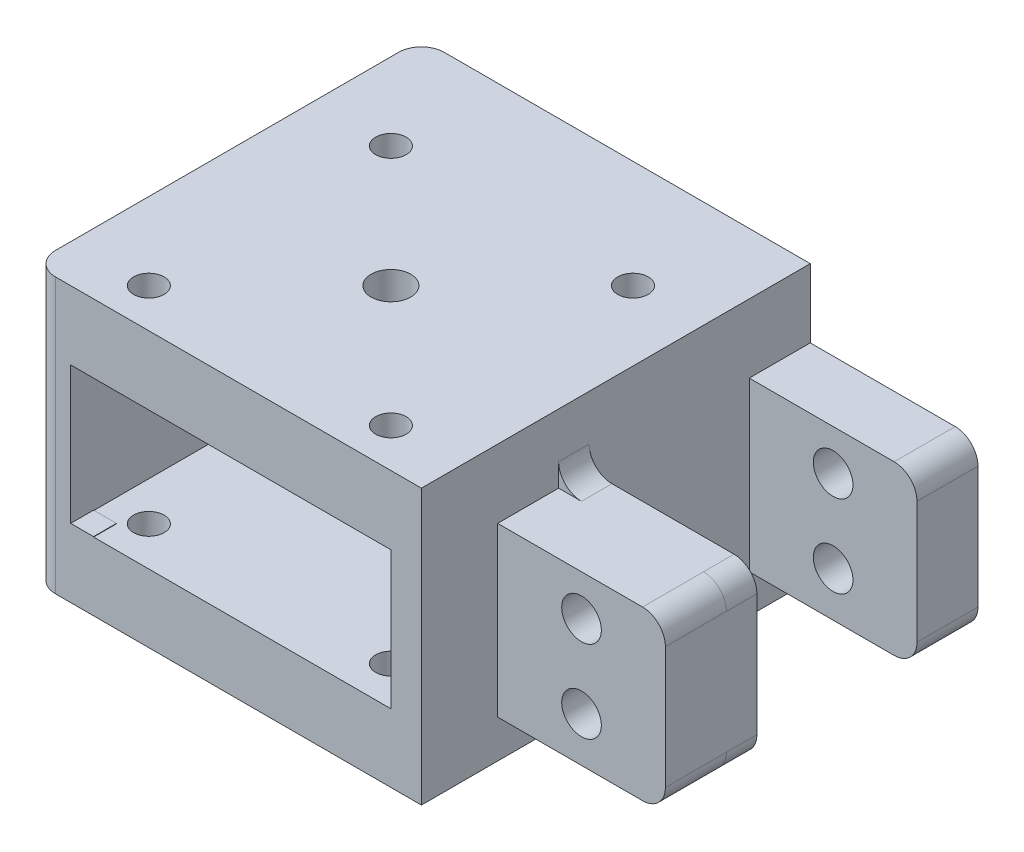
SolidWorks part; units mm, degrees
ref_plane "Front Plane" through (0, 0, 0) normal (0, 0, 1) x (1, 0, 0)
ref_plane "Top Plane" through (0, 0, 0) normal (0, 1, 0) x (1, 0, 0)
ref_plane "Right Plane" through (0, 0, 0) normal (1, 0, 0) x (0, 0, -1)
sketch "Sketch1" plane through (0, 0, 0) normal (0, 0, 1) x (1, 0, 0)
  line L1 (-11, -11) -> (11, -11)
  line L2 (-11, -11) -> (-11, 11)
  line L3 (-11, 11) -> (11, 11)
  line L4 (11, -11) -> (11, 11)
  line L5 (-11, -11) -> (11, 11) construction
  line L6 (-11, 11) -> (11, -11) construction
  point P0 (0, 0)
  dimension "D1" = 22
  dimension "D2" = 22
extrude "Boss-Extrude2" add sketch "Sketch1" along normal blind 4
sketch "Sketch3" plane through (0, 0, 4) normal (0, 0, 1) x (1, 0, 0)
  line L1 (-11, 11) -> (-15, 11)
  line L2 (-11, 11) -> (-11, -11)
  line L3 (-11, -11) -> (-15, -11)
  line L4 (-15, 11) -> (-15, -11)
  dimension "D1" = 4
extrude "Boss-Extrude3" add sketch "Sketch3" against normal blind 24
sketch "Sketch4" plane through (0, 11, 0) normal (0, 1, 0) x (1, 0, 0)
  line L1 (-11, 20) -> (-15, 20)
  line L2 (-11, 20) -> (-11, -4)
  line L3 (-11, -4) -> (-15, -4)
  line L4 (-15, 20) -> (-15, -4)
extrude "Boss-Extrude4" add sketch "Sketch4" along normal blind 4
sketch "Sketch5" plane through (-11, 0, 0) normal (1, 0, 0) x (0, 0, -1)
  line L1 (-4, 11) -> (20, 11)
  line L2 (-4, 11) -> (-4, 15)
  line L3 (-4, 15) -> (20, 15)
  line L4 (20, 11) -> (20, 15)
extrude "Boss-Extrude5" add sketch "Sketch5" against normal blind 24
sketch "Sketch6" plane through (-15, 0, 0) normal (-1, 0, 0) x (0, 0, 1)
  line L1 (-20, -11) -> (22, -11)
  line L2 (-20, -11) -> (-20, -7.0561)
  line L3 (-20, -7.0561) -> (22, -7.0561)
  line L4 (22, -11) -> (22, -7.0561)
  dimension "D1" = 42
extrude "Boss-Extrude6" add sketch "Sketch6" along normal blind 42
sketch "Sketch8" plane through (0, 15, 0) normal (0, 1, 0) x (1, 0, 0)
  line L0 (-11, 20) -> (-35, 20) construction
  line L1 (-57, -22) -> (-15, -22)
  line L2 (-57, -22) -> (-57, 20)
  line L3 (-57, 20) -> (-15, 20)
  line L4 (-15, -22) -> (-15, 20)
  line L5 (-57, 20) -> (-15, 20) construction
extrude "Boss-Extrude7" add sketch "Sketch8" against normal blind 4
sketch "Sketch9" plane through (0, -11, 0) normal (0, -1, 0) x (1, 0, 0)
  circle A0 centre (-36, 1) radius 11.5
  dimension "D1" = 23
extrude "Cut-Extrude1" cut sketch "Sketch9" against normal blind 4
sketch "Sketch10" plane through (0, 15, 0) normal (0, 1, 0) x (1, 0, 0)
  circle A0 centre (-34, -1) radius 2.6
  dimension "D1" = 5.2
extrude "Cut-Extrude2" cut sketch "Sketch10" against normal blind 4
sketch "Sketch11" plane through (0, 0, 4) normal (0, 0, 1) x (1, 0, 0)
  circle A0 centre (0, 5.6604) radius 2.6
  circle A1 centre (0, -5.136) radius 2.6
  dimension "D1" = 5.2
  dimension "D2" = 5.2
extrude "Cut-Extrude3" cut sketch "Sketch11" against normal blind 4
fillet "Fillet1" radius 3 10 edges at (-11, 11, 2) (11, 11, 2) (11, -11, 2) (-15, -9.0281, 22) (-57, -9.0281, 22) (-57, -9.0281, -20) (-57, 13, -20) (-11, 2, -20) (-15, 13, 22) (-57, 13, 22)
sketch "Sketch12" plane through (0, 15, 0) normal (0, 1, 0) x (1, 0, 0)
  line L1 (-40.0637, -6.0537) -> (-28.4493, -6.0537)
  line L2 (-40.0637, -6.0537) -> (-40.0637, 3.8424)
  line L3 (-40.0637, 3.8424) -> (-28.4493, 3.8424)
  line L4 (-28.4493, -6.0537) -> (-28.4493, 3.8424)
extrude "Boss-Extrude8" add sketch "Sketch12" against normal blind 4
sketch "Sketch13" plane through (0, 11, 0) normal (0, -1, 0) x (1, 0, 0)
  circle A0 centre (-36, 1) radius 2.6
  dimension "D1" = 5.2
extrude "Cut-Extrude5" cut sketch "Sketch13" against normal blind 4
sketch "Sketch15" plane through (0, -11, 0) normal (0, -1, 0) x (1, 0, 0)
  line L0 (-36, 1) -> (-20.1255, 16.8745) construction
  line L1 (-36, 1) -> (-51.8745, 16.8745) construction
  line L2 (-36, 1) -> (-51.8745, -14.8745) construction
  line L3 (-36, 1) -> (-20.1255, -14.8745) construction
  circle A0 centre (-20.1255, 16.8745) radius 2
  circle A1 centre (-51.8745, 16.8745) radius 2
  circle A2 centre (-51.8745, -14.8745) radius 2
  circle A3 centre (-20.1255, -14.8745) radius 2
  dimension "D2" = 4
  dimension "D3" = 4
  dimension "D4" = 4
  dimension "D5" = 4
  dimension "D1" = 22.45
extrude "Cut-Extrude7" cut sketch "Sketch15" against normal through all
sketch "Sketch16" plane through (0, -11, 0) normal (0, -1, 0) x (1, 0, 0)
  line L1 (-49.7323, 13.2384) -> (-22.3714, 13.2384)
  line L2 (-49.7323, 13.2384) -> (-49.7323, -11.3863)
  line L3 (-49.7323, -11.3863) -> (-22.3714, -11.3863)
  line L4 (-22.3714, 13.2384) -> (-22.3714, -11.3863)
extrude "Boss-Extrude11" add sketch "Sketch16" against normal blind 4
sketch "Sketch17" plane through (0, -11, 0) normal (0, -1, 0) x (1, 0, 0)
  circle A0 centre (-36, 1) radius 2.6
extrude "Cut-Extrude8" cut sketch "Sketch17" against normal through all
sketch "Sketch18" plane through (-49.7323, 0, 0) normal (-1, 0, 0) x (0, 0, 1)
  line L1 (13.2384, -7) -> (-11.3863, -7)
  line L2 (13.2384, -7) -> (13.2384, -7.0561)
  line L3 (13.2384, -7.0561) -> (-11.3863, -7.0561)
  line L4 (-11.3863, -7) -> (-11.3863, -7.0561)
extrude "Cut-Extrude9" cut sketch "Sketch18" against normal blind 34
sketch "Sketch19" plane through (0, -11, 0) normal (0, -1, 0) x (1, 0, 0)
  line L1 (-11, -20) -> (-57, -20)
  line L2 (-11, -20) -> (-11, 22)
  line L3 (-11, 22) -> (-57, 22)
  line L4 (-57, -20) -> (-57, 22)
extrude "Boss-Extrude12" add sketch "Sketch19" along normal blind 5
fillet "Fillet2" radius 3 1 edges at (-57, -13.5, 22)
fillet "Fillet3" radius 3 1 edges at (-57, -13.5, -20)
fillet "Fillet4" radius 3 1 edges at (-11, -13.5, -20)
sketch "Sketch20" plane through (0, 15, 0) normal (0, 1, 0) x (1, 0, 0)
  line L1 (-11, 20) -> (-57, 20)
  line L2 (-11, 20) -> (-11, -22)
  line L3 (-11, -22) -> (-57, -22)
  line L4 (-57, 20) -> (-57, -22)
extrude "Boss-Extrude13" add sketch "Sketch20" along normal blind 5
fillet "Fillet5" radius 3 1 edges at (-11, 17.5, -20)
fillet "Fillet6" radius 3 1 edges at (-57, 17.5, -20)
fillet "Fillet7" radius 3 1 edges at (-57, 17.5, 22)
sketch "Sketch25" plane through (0, -7.0561, 0) normal (0, 1, 0) x (1, 0, 0)
  circle A0 centre (-51.8745, -16.8745) radius 2
extrude "Cut-Extrude10" cut sketch "Sketch25" against normal through all
sketch "Sketch26" plane through (0, -7.0561, 0) normal (0, 1, 0) x (1, 0, 0)
  circle A0 centre (-20.1255, -16.8745) radius 2
extrude "Cut-Extrude11" cut sketch "Sketch26" against normal through all
sketch "Sketch28" plane through (0, -7.0561, 0) normal (0, 1, 0) x (1, 0, 0)
  circle A0 centre (-36, -1) radius 2.6
extrude "Cut-Extrude12" cut sketch "Sketch28" against normal through all
sketch "Sketch29" plane through (0, -7.0561, 0) normal (0, 1, 0) x (1, 0, 0)
  circle A0 centre (-51.8745, 14.8745) radius 2
extrude "Cut-Extrude13" cut sketch "Sketch29" against normal through all
sketch "Sketch30" plane through (0, -7.0561, 0) normal (0, 1, 0) x (1, 0, 0)
  circle A0 centre (-20.1255, 14.8745) radius 2
extrude "Cut-Extrude14" cut sketch "Sketch30" against normal through all
sketch "Sketch31" plane through (0, 11, 0) normal (0, -1, 0) x (1, 0, 0)
  circle A0 centre (-51.8745, -14.8745) radius 2
  circle A1 centre (-20.1255, -14.8745) radius 2
  circle A2 centre (-36, 1) radius 2.6
  circle A3 centre (-51.8745, 16.8745) radius 2
  circle A4 centre (-20.1255, 16.8745) radius 2
extrude "Cut-Extrude15" cut sketch "Sketch31" against normal through all
sketch "Sketch32" plane through (0, 0, 4) normal (0, 0, 1) x (1, 0, 0)
  line L1 (-15, 15) -> (-11, 15)
  line L2 (-15, 15) -> (-15, -11)
  line L3 (-15, -11) -> (-11, -11)
  line L4 (-11, 15) -> (-11, -11)
extrude "Boss-Extrude19" add sketch "Sketch32" along normal blind 18
sketch "Sketch33" plane through (0, 0, 4) normal (0, 0, 1) x (1, 0, 0)
  line L1 (-11, -11) -> (11, -11)
  line L2 (-11, -11) -> (-11, 11)
  line L3 (-11, 11) -> (11, 11)
  line L4 (11, -11) -> (11, 11)
extrude "Boss-Extrude20" add sketch "Sketch33" along normal blind 8
fillet "Fillet8" radius 3 1 edges at (11, 11, 8)
fillet "Fillet9" radius 3 1 edges at (11, -11, 8)
sketch "Sketch34" plane through (0, 0, 0) normal (0, 0, -1) x (-1, 0, 0)
  circle A0 centre (0, 5.6604) radius 2.6
  circle A1 centre (0, -5.136) radius 2.6
extrude "Cut-Extrude16" cut sketch "Sketch34" against normal through all
sketch "Sketch35" plane through (0, 0, 22) normal (0, 0, 1) x (1, 0, 0)
  line L1 (-18, 11) -> (-15, 11)
  line L2 (-18, 11) -> (-18, 15)
  line L3 (-18, 15) -> (-15, 15)
  line L4 (-15, 11) -> (-15, 15)
  line L5 (-18, -7.0561) -> (-15, -7.0561)
  line L6 (-18, -7.0561) -> (-18, -11)
  line L7 (-18, -11) -> (-15, -11)
  line L8 (-15, -7.0561) -> (-15, -11)
extrude "Boss-Extrude21" add sketch "Sketch35" against normal blind 8
sketch "Sketch36" plane through (0, 20, 0) normal (0, 1, 0) x (1, 0, 0)
  line L0 (-57, 17) -> (-11, 17)
  line L1 (-11, 17) -> (-11, 20)
  line L2 (-11, 20) -> (-57, 20)
  line L3 (-57, 20) -> (-57, 17)
extrude "Boss-Extrude22" add sketch "Sketch36" against normal blind 9
sketch "Sketch37" plane through (0, -16, 0) normal (0, -1, 0) x (1, 0, 0)
  line L1 (-57, -17) -> (-11, -17)
  line L2 (-57, -17) -> (-57, -20)
  line L3 (-57, -20) -> (-11, -20)
  line L4 (-11, -17) -> (-11, -20)
extrude "Boss-Extrude23" add sketch "Sketch37" against normal blind 9
sketch "Sketch38" plane through (0, 20, 0) normal (0, 1, 0) x (1, 0, 0)
  line L1 (-57, 20) -> (-11, 20)
  line L2 (-57, 20) -> (-57, 29)
  line L3 (-57, 29) -> (-11, 29)
  line L4 (-11, 20) -> (-11, 29)
  dimension "D1" = 9
extrude "Boss-Extrude24" add sketch "Sketch38" against normal through all
sketch "Sketch39" plane through (0, 0, -20) normal (0, 0, 1) x (1, 0, 0)
  line L1 (-57, 11) -> (-15, 11)
  line L2 (-57, 11) -> (-57, -7.0561)
  line L3 (-57, -7.0561) -> (-15, -7.0561)
  line L4 (-15, 11) -> (-15, -7.0561)
extrude "Cut-Extrude17" cut sketch "Sketch39" against normal through all
sketch "Sketch40" plane through (-11, 0, 0) normal (1, 0, 0) x (0, 0, -1)
  line L1 (17, 11) -> (20, 11)
  line L2 (17, 11) -> (17, -7)
  line L3 (17, -7) -> (20, -7)
  line L4 (20, 11) -> (20, -7)
extrude "Boss-Extrude25" add sketch "Sketch40" against normal blind 3
sketch "Sketch41" plane through (-11, 0, 0) normal (1, 0, 0) x (0, 0, -1)
  line L0 (29, -16) -> (29, 20) construction
  line L1 (29, 11) -> (19.4, 11)
  line L2 (29, 11) -> (29, -11)
  line L3 (29, -11) -> (19.4, -11)
  line L4 (19.4, 11) -> (19.4, -11)
  dimension "D1" = 9.6
extrude "Boss-Extrude26" add sketch "Sketch41" along normal up to vertex (22 mm away) up to point (11, -8, 12)
sketch "Sketch42" plane through (0, 0, 12) normal (0, 0, 1) x (1, 0, 0)
  circle A0 centre (0, 5.6604) radius 2.6
  circle A1 centre (0, -5.136) radius 2.6
extrude "Cut-Extrude18" cut sketch "Sketch42" against normal through all
fillet "Fillet10" radius 3 2 edges at (11, -11, -24.2) (11, 11, -24.2)
sketch "Sketch43" plane through (-11, 0, 0) normal (1, 0, 0) x (0, 0, -1)
  line L0 (19.4, -11) -> (29, -11) construction
  line L1 (19.4, 11) -> (21, 11)
  line L2 (19.4, 11) -> (19.4, -11)
  line L3 (19.4, -11) -> (21, -11)
  line L4 (21, 11) -> (21, -11)
  dimension "D1" = 1.6
extrude "Cut-Extrude19" cut sketch "Sketch43" along normal through all
sketch "Sketch45" plane through (0, 20, 0) normal (0, 1, 0) x (1, 0, 0)
  line L1 (-57, 29) -> (-62, 29)
  line L2 (-57, 29) -> (-57, -22)
  line L3 (-57, -22) -> (-62, -22)
  line L4 (-62, 29) -> (-62, -22)
  dimension "D1" = 5
extrude "Boss-Extrude27" add sketch "Sketch45" against normal through all
sketch "Sketch46" plane through (0, 20, 0) normal (0, 1, 0) x (1, 0, 0)
  line L1 (-54, -22) -> (-57, -22)
  line L2 (-54, -22) -> (-54, -19)
  line L3 (-54, -19) -> (-57, -19)
  line L4 (-57, -22) -> (-57, -19)
extrude "Boss-Extrude28" add sketch "Sketch46" against normal blind 9
sketch "Sketch47" plane through (0, -16, 0) normal (0, -1, 0) x (1, 0, 0)
  line L1 (-54, 22) -> (-57, 22)
  line L2 (-54, 22) -> (-54, 19)
  line L3 (-54, 19) -> (-57, 19)
  line L4 (-57, 22) -> (-57, 19)
extrude "Boss-Extrude29" add sketch "Sketch47" against normal blind 9
fillet "Fillet11" radius 3 1 edges at (-62, 2, 22)
fillet "Fillet12" radius 3 1 edges at (-62, 2, -29)
